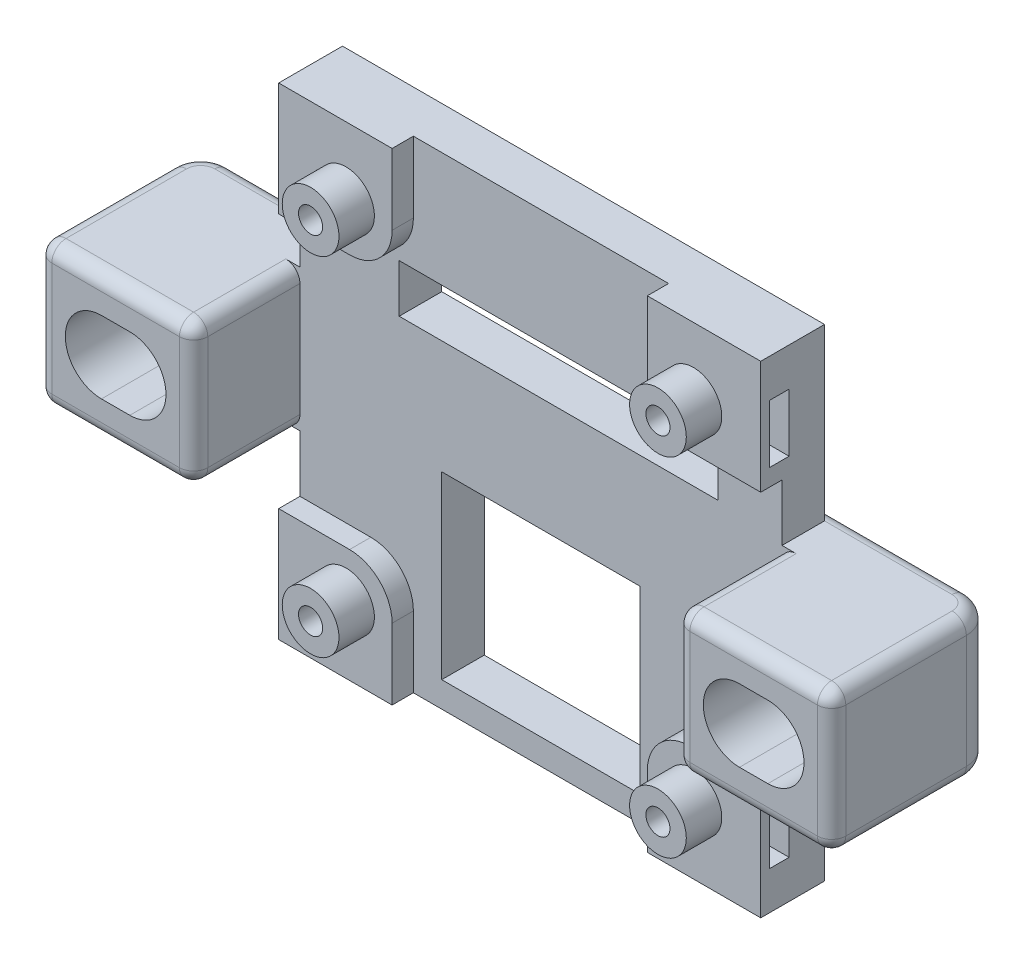
SolidWorks part; units mm, degrees
ref_plane "Front Plane" through (0, 0, 0) normal (0, 0, 1) x (1, 0, 0)
ref_plane "Top Plane" through (0, 0, 0) normal (0, 1, 0) x (1, 0, 0)
ref_plane "Right Plane" through (0, 0, 0) normal (1, 0, 0) x (0, 0, -1)
sketch "Sketch2" plane through (0, 0, 0) normal (0, 0, 1) x (1, 0, 0)
  line L1 (-17, -17) -> (17, -17)
  line L2 (-17, -17) -> (-17, 17)
  line L3 (-17, 17) -> (17, 17)
  line L4 (17, -17) -> (17, 17)
  line L5 (-17, -17) -> (17, 17) construction
  line L6 (-17, 17) -> (17, -17) construction
  point P0 (0, 0)
  dimension "D1" = 34
  dimension "D2" = 34
extrude "Boss-Extrude Main" add sketch "Sketch2" along normal blind 4.5
sketch "Sketch9" plane through (0, 0, 4.5) normal (0, 0, 1) x (1, 0, 0)
  line L0 (-4.9023, -6) -> (11.0724, -6) construction
  line L1 (-7, -15.2) -> (7, -15.2)
  line L2 (-7, -15.2) -> (-7, -2.5)
  line L3 (-7, -2.5) -> (7, -2.5)
  line L4 (7, -15.2) -> (7, -2.5)
  point P4 (0, -2.5)
  dimension "D1" = 12.7
  dimension "D2" = 14
  dimension "D3" = 3.5
  dimension "D4" = 7
  dimension "D5" = 6
extrude "Cut-USBc hole" cut sketch "Sketch9" against normal through all
sketch "Sketch10" plane through (0, 0, 4.5) normal (0, 0, 1) x (1, 0, 0)
  line L0 (-17, 17) -> (-17, -17) construction
  line L1 (-10, 8.9) -> (12.5, 8.9)
  line L2 (-10, 8.9) -> (-10, 5.5)
  line L3 (-10, 5.5) -> (12.5, 5.5)
  line L4 (12.5, 8.9) -> (12.5, 5.5)
  line L5 (17, -17) -> (17, 17) construction
  dimension "D1" = 3.4
  dimension "D2" = 4.5
  dimension "D3" = 5.5
  dimension "D4" = 7
extrude "Cut-FourPin Notch" cut sketch "Sketch10" against normal blind 15.7
sketch "Sketch11" plane through (0, 0, 4.5) normal (0, 0, 1) x (1, 0, 0)
  circle A0 centre (-12.25, 12.25) radius 2
  circle A1 centre (12.25, 12.25) radius 2
  circle A2 centre (12.25, -12.25) radius 2
  circle A3 centre (-12.25, -12.25) radius 2
  dimension "D1" = 4
  dimension "D2" = 4
  dimension "D3" = 4
  dimension "D4" = 4
extrude "Boss-Extrude_PegSpacers" add sketch "Sketch11" along normal blind 2.5
hole_wizard "Ø2.0mm Holes for Pegs" positions "3DSketch1" profile "Sketch12" hole size "Ø2.0" standard "ANSI Metric"
sketch3d "3DSketch1"
  line L0 (-12.25, 12.25, 7) -> (-12.25, 12.25, 4.5) construction
  line L1 (12.25, 12.25, 7) -> (12.25, 12.25, 4.5) construction
  line L2 (12.25, -12.25, 7) -> (12.25, -12.25, 4.5) construction
  line L3 (-12.25, -12.25, 7) -> (-12.25, -12.25, 4.5) construction
  point P0 (-12.25, 12.25, 7)
  point P4 (12.25, 12.25, 7)
  point P8 (12.25, -12.25, 7)
  point P12 (-12.25, -12.25, 7)
sketch "Sketch12" plane through (-12.25, 12.25, 7) normal (1, 0, 0) x (0, -1, 0)
  line L0 (0, 0) -> (0, 4.5107)
  line L1 (0, 4.5107) -> (0.85, 4)
  line L2 (0.85, 4) -> (0.85, 0)
  line L5 (0.85, 0) -> (0, 0)
  line L10 (0, 4.5107) -> (-0.85, 4) construction
  line L11 (0, -6.35) -> (0, 107.95) construction
  dimension "Hole Dia." = 1.7
  dimension "Hole Depth" = 4
  dimension "Drill Angle" = 118
sketch "Sketch15" plane through (0, 0, 0) normal (0, 0, -1) x (-1, 0, 0)
  circle A0 centre (0, -11) radius 15.4
  circle A1 centre (0, -11) radius 12
  dimension "D1" = 11
  dimension "D2" = 30.8
  dimension "D3" = 24
other "AlignGroup1"
extrude "Cut-SM1" cut sketch "Sketch15" against normal blind 1
sketch "Sketch18" plane through (17, 0, 0) normal (1, 0, 0) x (0, 0, -1)
  line L0 (-4.5, -10.25) -> (-7, -10.25) construction
  line L1 (-3.9, -10.2) -> (-2.5, -10.2)
  line L2 (-3.9, -10.2) -> (-3.9, -14.3)
  line L3 (-3.9, -14.3) -> (-2.5, -14.3)
  line L4 (-2.5, -10.2) -> (-2.5, -14.3)
  line L5 (-4.5, -17) -> (-4.5, 17) construction
  line L10 (-7, 10.25) -> (-4.5, 10.25) construction
  line L11 (-3.9, 14.3) -> (-2.5, 14.3)
  line L12 (-3.9, 14.3) -> (-3.9, 10.2)
  line L13 (-3.9, 10.2) -> (-2.5, 10.2)
  line L14 (-2.5, 14.3) -> (-2.5, 10.2)
  line L15 (-4.5, 14.25) -> (-4.5, 10.25) construction
  dimension "D1" = 1.4
  dimension "D2" = 4.1
  dimension "D3" = 0.05
  dimension "D4" = 0.6
  dimension "D5" = 0.05
  dimension "D6" = 0.6
  dimension "D7" = 4.1
  dimension "D8" = 4.1
sketch "Sketch19" plane through (-17, 0, 0) normal (-1, 0, 0) x (0, 0, 1)
  line L0 (4.5, -14.25) -> (7, -14.25) construction
  line L1 (3.9, 14.3) -> (2.5, 14.3)
  line L2 (3.9, 14.3) -> (3.9, 10.2)
  line L3 (3.9, 10.2) -> (2.5, 10.2)
  line L4 (2.5, 14.3) -> (2.5, 10.2)
  line L5 (2.5, -10.2) -> (3.9, -10.2)
  line L6 (2.5, -10.2) -> (2.5, -14.3)
  line L7 (2.5, -14.3) -> (3.9, -14.3)
  line L8 (3.9, -10.2) -> (3.9, -14.3)
  line L9 (7, 14.25) -> (4.5, 14.25) construction
  line L11 (4.5, 17) -> (4.5, -17) construction
  dimension "D1" = 1.4
  dimension "D2" = 1.4
  dimension "D3" = 0.6
  dimension "D4" = 4.1
  dimension "D5" = 0.6
  dimension "D6" = 0.05
  dimension "D7" = 0.05
extrude "Cut-HexNutRight" cut sketch "Sketch18" against normal blind 6.75 and the other way through all
extrude "Cut-HexNutLeft" cut sketch "Sketch19" against normal blind 6.75
sketch "Sketch20" plane through (0, 0, 4.5) normal (0, 0, 1) x (1, 0, 0)
  line L10 (17, 17) -> (-17, 17) construction
  line L11 (-9, 17) -> (9, 17)
  line L12 (-9, 17) -> (-9, -17)
  line L13 (-9, -17) -> (9, -17)
  line L14 (9, 17) -> (9, -17)
  line L15 (-17, -17) -> (17, -17) construction
  line L16 (-17, 17) -> (-17, -17) construction
  line L18 (17, -17) -> (17, 17) construction
  dimension "D1" = 8
  dimension "D2" = 0
  dimension "D3" = 0
  dimension "D4" = 8
extrude "Cut-Extrude2" cut sketch "Sketch20" against normal blind 1.5
sketch "Sketch21" plane through (0, 0, 4.5) normal (0, 0, 1) x (1, 0, 0)
  line L0 (17, -17) -> (17, 17) construction
  line L1 (17, 9) -> (-17, 9)
  line L2 (17, 9) -> (17, -9)
  line L3 (17, -9) -> (-17, -9)
  line L4 (-17, 9) -> (-17, -9)
  line L5 (-17, 17) -> (-17, -17) construction
  line L6 (-9, -17) -> (9, -17) construction
  line L7 (9, 17) -> (-9, 17) construction
  dimension "D1" = 8
  dimension "D2" = 8
extrude "Cut-Extrude3" cut sketch "Sketch21" against normal blind 1.5
sketch "Sketch22" plane through (0, 0, 0) normal (0, 0, 1) x (1, 0, 0)
  line L0 (17, -17) -> (17, 17) construction
  line L1 (-28, -5) -> (-15, -5)
  line L2 (-28, -5) -> (-28, 5)
  line L3 (-28, 5) -> (-15, 5)
  line L4 (-15, -5) -> (-15, 5)
  line L5 (15, -5) -> (28, -5)
  line L6 (15, -5) -> (15, 5)
  line L7 (15, 5) -> (28, 5)
  line L8 (28, -5) -> (28, 5)
  line L9 (-17, 17) -> (-17, -17) construction
  dimension "D1" = 10
  dimension "D2" = 10
  dimension "D3" = 5
  dimension "D4" = 5
  dimension "D5" = 13
  dimension "D6" = 13
  dimension "D7" = 2
  dimension "D8" = 2
extrude "Boss-Extrude1" add sketch "Sketch22" along normal blind 10.5
sketch "Sketch24" plane through (0, 0, 0) normal (0, 0, -1) x (-1, 0, 0)
  line L0 (21.5, 0) -> (23.5, 0) construction
  line L1 (21.5, 2.55) -> (23.5, 2.55)
  line L2 (21.5, -2.55) -> (23.5, -2.55)
  line L3 (-21.5, 0) -> (-23.5, 0) construction
  line L4 (-21.5, -2.55) -> (-23.5, -2.55)
  line L5 (-21.5, 2.55) -> (-23.5, 2.55)
  line L6 (28, 5) -> (28, -5) construction
  arc A0 (21.5, 2.55) -> (21.5, -2.55) centre (21.5, 0) ccw
  arc A1 (23.5, -2.55) -> (23.5, 2.55) centre (23.5, 0) ccw
  arc A2 (-21.5, -2.55) -> (-21.5, 2.55) centre (-21.5, 0) ccw
  arc A3 (-23.5, 2.55) -> (-23.5, -2.55) centre (-23.5, 0) ccw
  point P3 (22.5, 0)
  point P8 (-22.5, 0)
  dimension "D1" = 2.55
  dimension "D2" = 2
  dimension "D3" = 2.55
  dimension "D4" = 2
  dimension "D5" = 45
  dimension "D6" = 5.5
extrude "Cut-Extrude4" cut sketch "Sketch24" against normal blind 15
sketch "Sketch25" plane through (0, 0, 3) normal (0, 0, 1) x (1, 0, 0)
  line L0 (15, -5) -> (28, -5) construction
  line L1 (-17, 5) -> (-15, 5)
  line L2 (-17, 5) -> (-17, -5)
  line L3 (-17, -5) -> (-15, -5)
  line L4 (-15, 5) -> (-15, -5)
  line L5 (15, 5) -> (17, 5)
  line L6 (15, 5) -> (15, -5)
  line L7 (15, -5) -> (17, -5)
  line L8 (17, 5) -> (17, -5)
extrude "Cut-Extrude5" cut sketch "Sketch25" along normal blind 15
extrude "Boss-Extrude2" add sketch "Sketch22<2>" against normal blind 1
sketch "Sketch22<2>" plane through (0, 0, 0) normal (0, 0, 1) x (1, 0, 0) same geometry as "Sketch22"
extrude "Cut-Extrude6" cut sketch "Sketch24<2>" along normal blind 2
sketch "Sketch24<2>" plane through (0, 0, 0) normal (0, 0, -1) x (-1, 0, 0) same geometry as "Sketch24"
fillet "Fillet5" radius 3 1 edges at (-9, -9, 3.75) type face fillet first side face at (-9, -13, 3.75) second side face at (-13, -9, 3.75)
fillet "Fillet4" radius 3 1 edges at (9, -9, 3.75) type face fillet first side face at (13, -9, 3.75) second side face at (9, -13, 3.75)
fillet "Fillet3" radius 3 1 edges at (-9, 9, 3.75) type face fillet first side face at (-9, 13, 3.75) second side face at (-13, 9, 3.75)
fillet "Fillet2" radius 3 1 edges at (9, 9, 3.75) type face fillet first side face at (9, 13, 3.75) second side face at (13, 9, 3.75)
fillet "Fillet7" radius 2 1 edges at (-28, 0, -1) type face fillet first side face at (-21.5, 0, -1) second side face at (-28, 0, 4.75)
fillet "Fillet8" radius 2 1 edges at (28, 0, -1) type face fillet first side face at (21.5, 0, -1) second side face at (28, 0, 4.75)
fillet "Fillet9" radius 1 1 edges at (-28, 0, 10.5) type face fillet first side face at (-28, 0, 5.75) second side face at (-22.5, 0, 10.5)
fillet "Fillet10" radius 1 1 edges at (-22, 5, 10.5) type face fillet first side face at (-21.1801, 5, 3.5881) second side face at (-22.5, 0, 10.5)
fillet "Fillet11" radius 1 1 edges at (-17, -0.5, 10.5) type face fillet first side face at (-17, 0.8414, 7.3414) second side face at (-22.5, 0, 10.5)
fillet "Fillet12" radius 1 1 edges at (-22.5, -5, 10.5) type face fillet first side face at (-20.8414, -5, 4.2) second side face at (-22.5, 0, 10.5)
fillet "Fillet13" radius 1 1 edges at (28, -5, 5.75) type face fillet first side face at (20.4268, -5, 2.8232) second side face at (28, 0, 5.75)
fillet "Fillet14" radius 1 1 edges at (28, 5, 5.75) type face fillet first side face at (28, 0.5, 5.75) second side face at (20.4268, 5, 2.8232)
fillet "Fillet15" radius 1 1 edges at (28, 0, 10.5) type face fillet first side face at (28, 0, 5.75) second side face at (22.5, 0, 10.5)
fillet "Fillet16" radius 1 1 edges at (17, 0, 10.5) type face fillet first side face at (22.5, 0, 10.5) second side face at (17, 0, 7.7357)
